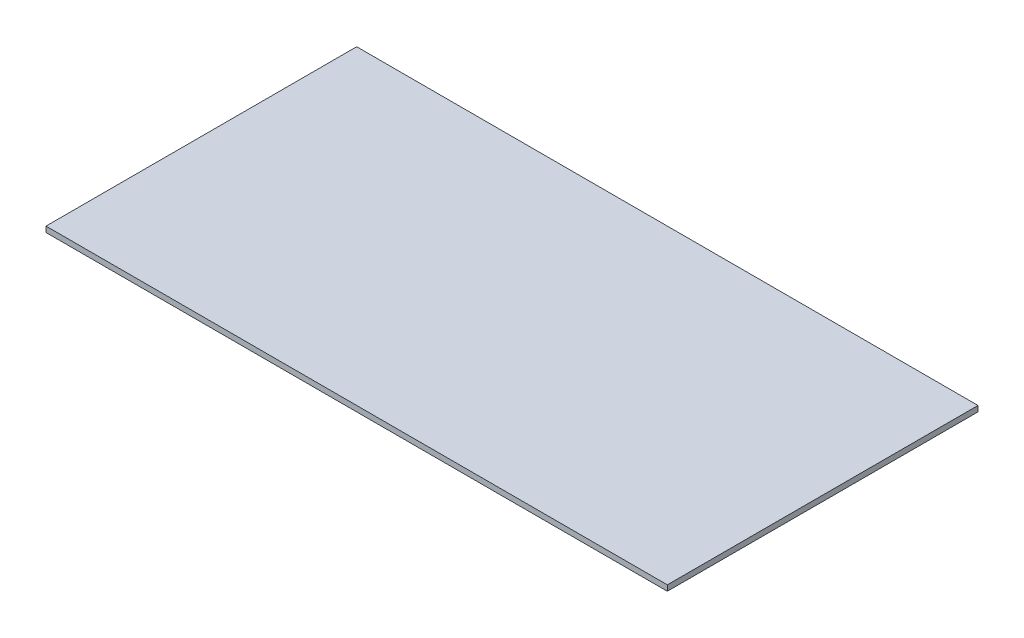
SolidWorks part; units mm, degrees
material "ABS"
ref_plane "Front Plane" through (0, 0, 0) normal (0, 0, 1) x (1, 0, 0)
ref_plane "Top Plane" through (0, 0, 0) normal (0, 1, 0) x (1, 0, 0)
ref_plane "Right Plane" through (0, 0, 0) normal (1, 0, 0) x (0, 0, -1)
sketch "Sketch1" plane through (0, 0, 0) normal (0, 1, 0) x (1, 0, 0)
  line L1 (0, 0) -> (2000, 0)
  line L2 (0, 0) -> (0, 1000)
  line L3 (0, 1000) -> (2000, 1000)
  line L4 (2000, 0) -> (2000, 1000)
  dimension "D1" = 1000
  dimension "D2" = 2000
extrude "Boss-Extrude1" add sketch "Sketch1" along normal blind 18
